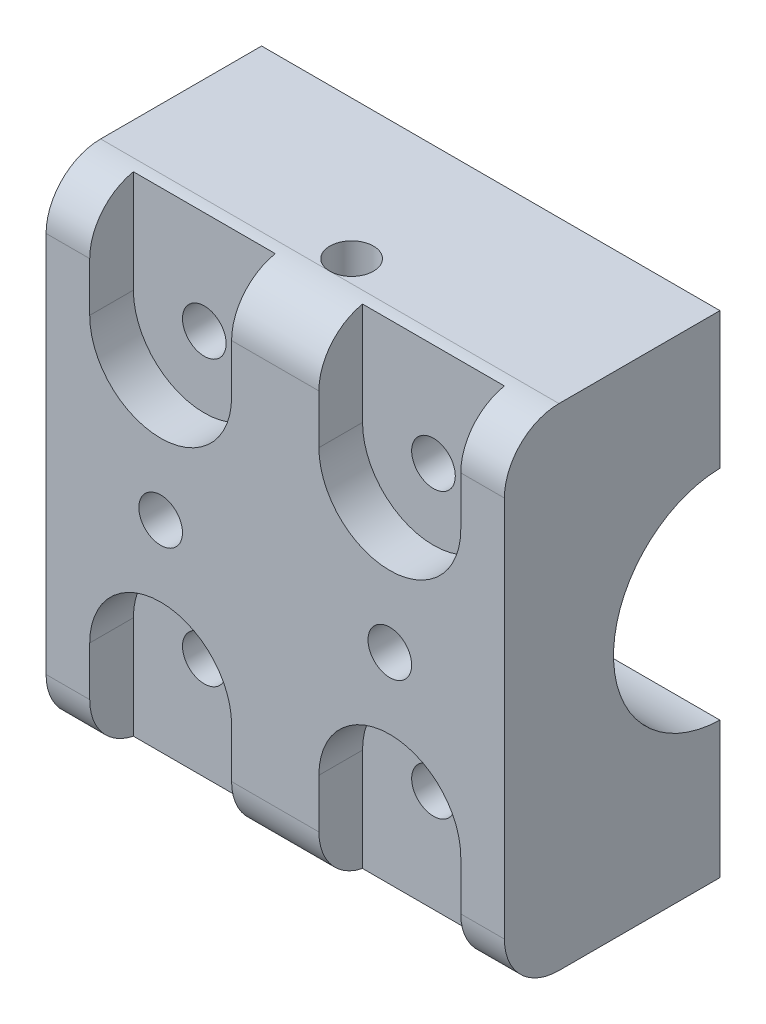
SolidWorks part; units mm, degrees
material "Custom Plastic"
ref_plane "Front Plane" through (0, 0, 0) normal (0, 0, 1) x (1, 0, 0)
ref_plane "Top Plane" through (0, 0, 0) normal (0, 1, 0) x (1, 0, 0)
ref_plane "Right Plane" through (0, 0, 0) normal (1, 0, 0) x (0, 0, -1)
sketch "Sketch1" plane through (0, 0, 0) normal (1, 0, 0) x (0, 0, -1)
  line L0 (0, 22.5) -> (0, -22.5) construction
  line L1 (-0.25, 22.5) -> (-0.25, 9.9969)
  line L2 (-0.25, -9.9969) -> (-0.25, -22.5)
  line L4 (-0.25, 22.5) -> (-0.25, -22.5) construction
  line L6 (-20, 17.5) -> (-20, -17.5)
  line L8 (0, 22.5) -> (-15, 22.5)
  line L10 (0, 0) -> (-20, 0) construction
  line L12 (0, -22.5) -> (-15, -22.5)
  arc A1 (0, 10) -> (0, -10) centre (0, 0) ccw
  circle A3 centre (0, 0) radius 10 construction
  arc A4 (-15, 22.5) -> (-20, 17.5) centre (-15, 17.5) ccw
  arc A5 (-20, -17.5) -> (-15, -22.5) centre (-15, -17.5) ccw
  point P23 (-10, 0)
  dimension "D2" = 45
  dimension "D4" = 5
  dimension "D3" = 20
  dimension "D1" = 0.25
extrude "Boss-Extrude1" add sketch "Sketch1" against normal blind 42 contours A1 L1 L2 region at (0, 0, 11.1992)
sketch "Sketch2" plane through (0, 0, 0.25) normal (0, 0, 1) x (1, 0, 0)
  line L0 (0, 0) -> (-42, 0) construction
  line L2 (-42, 13) -> (-21, 13) construction
  line L3 (-10.5, 11) -> (-31.5, 11) construction
  line L4 (-42, 22.5) -> (0, 22.5) construction
  line L5 (-21, 22.5) -> (-21, -22.5) construction
  line L7 (-42, 17.5) -> (-42, -17.5) construction
  line L8 (-42, 17.5) -> (-42, -17.5) construction
  line L9 (-42, -22.5) -> (0, -22.5) construction
  circle A0 centre (-31.5, 13) radius 2
  circle A1 centre (-10.5, 13) radius 2
  circle A2 centre (-10.5, -13) radius 2
  circle A3 centre (-31.5, -13) radius 2
  point P21 (-21, 11)
  dimension "D2" = 4
  dimension "D1" = 13
extrude "Cut-Extrude2" cut sketch "Sketch2" along normal through all contours A1 | A0 | A3 | A2 region at (-31.5, 13, 0.25) region at (-10.5, 13, 0.25) region at (-10.5, -13, 0.25) region at (-31.5, -13, 0.25)
sketch "Sketch3" plane through (0, 0, 20) normal (0, 0, 1) x (1, 0, 0)
  line L0 (0, 0) -> (-42, 0) construction
  line L1 (-42, 22.5) -> (0, 22.5) construction
  line L2 (-38, 13) -> (-38, 22.5)
  line L3 (-38, 22.5) -> (-25, 22.5)
  line L4 (-25, 22.5) -> (-25, 13)
  line L5 (-17, 13) -> (-17, 22.5)
  line L6 (-17, 22.5) -> (-4, 22.5)
  line L7 (-4, 22.5) -> (-4, 13)
  line L8 (-4, -22.5) -> (-4, -13)
  line L9 (-17, -22.5) -> (-4, -22.5)
  line L10 (-17, -13) -> (-17, -22.5)
  line L11 (-25, -22.5) -> (-25, -13)
  line L12 (-38, -22.5) -> (-25, -22.5)
  line L13 (-38, -13) -> (-38, -22.5)
  line L14 (-42, 17.5) -> (-42, -17.5) construction
  arc A0 (-38, 13) -> (-25, 13) centre (-31.5, 13) ccw
  arc A1 (-17, 13) -> (-4, 13) centre (-10.5, 13) ccw
  arc A2 (-17, -13) -> (-4, -13) centre (-10.5, -13) cw
  arc A3 (-38, -13) -> (-25, -13) centre (-31.5, -13) cw
  dimension "D1" = 13
extrude "Cut-Extrude3" cut sketch "Sketch3" against normal blind 4
sketch "Sketch4" plane through (0, 0, 20) normal (0, 0, 1) x (1, 0, 0)
  circle A0 centre (-10.5, 0) radius 2
  circle A1 centre (-31.5, 0) radius 2
  circle A2 centre (-10.5, 0) radius 2 construction
extrude "Cut-Extrude4" cut sketch "Sketch4" against normal through all
sketch "Sketch5" plane through (0, -22.5, 0) normal (0, -1, 0) x (1, 0, 0)
  line L0 (-21, 20) -> (-21, 0.25) construction
  line L3 (-25, 20) -> (-17, 20) construction
  line L4 (-42, 0.25) -> (0, 0.25) construction
  line L5 (-42, 15) -> (0, 15) construction
  circle A0 centre (-21, 13) radius 2
  dimension "D1" = 4
extrude "Cut-Extrude5" cut sketch "Sketch5" against normal through all
